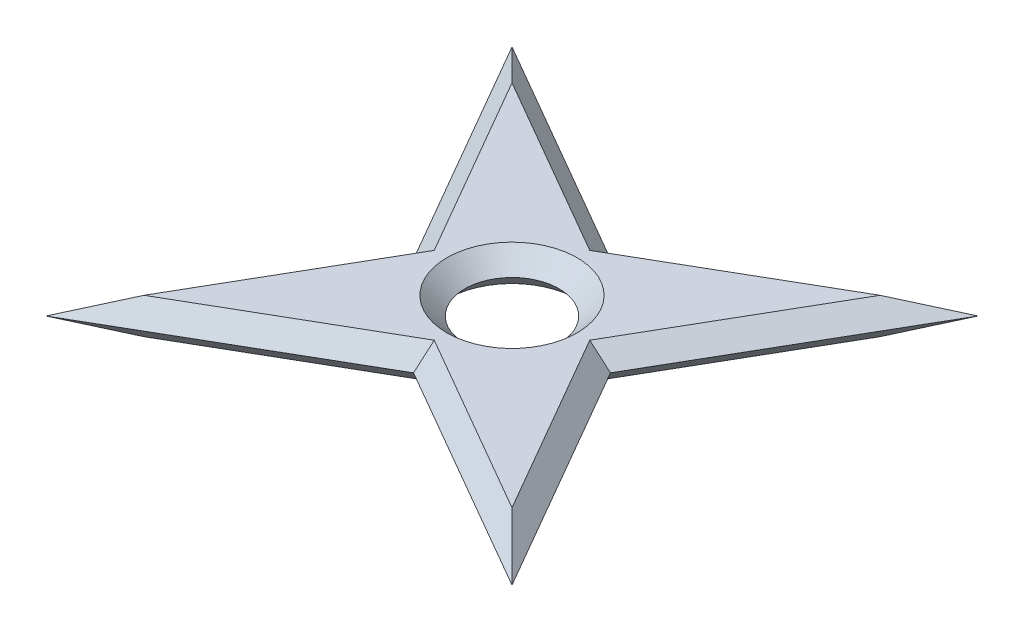
SolidWorks part; units mm, degrees
ref_plane "Front Plane" through (0, 0, 0) normal (0, 0, 1) x (1, 0, 0)
ref_plane "Top Plane" through (0, 0, 0) normal (0, 1, 0) x (1, 0, 0)
ref_plane "Right Plane" through (0, 0, 0) normal (1, 0, 0) x (0, 0, -1)
sketch "Sketch1" plane through (0, 0, 0) normal (0, 1, 0) x (1, 0, 0)
  line L0 (0, 0) -> (0, 234.4789) construction
  line L1 (0, 0) -> (250.2537, 0) construction
  line L2 (0, 0) -> (37.5, 64.9519)
  line L3 (0, 0) -> (64.9519, 37.5)
  line L5 (64.9519, 64.9519) -> (64.9519, 0) construction
  line L6 (129.9038, 0) -> (64.9519, 37.5)
  line L7 (129.9038, 0) -> (92.4038, 64.9519)
  line L8 (37.5, 64.9519) -> (92.4038, 64.9519) construction
  line L9 (129.9038, 129.9038) -> (92.4038, 64.9519)
  line L10 (129.9038, 129.9038) -> (64.9519, 92.4038)
  line L11 (0, 129.9038) -> (64.9519, 92.4038)
  line L12 (0, 129.9038) -> (37.5, 64.9519)
  circle A0 centre (64.9519, 64.9519) radius 13.155
  dimension "D5" = 26.31
  dimension "D1" = 75
  dimension "D2" = 30
  dimension "D3" = 30
  dimension "D4" = 75
extrude "Boss-Extrude1" add sketch "Sketch1" along normal blind 10
chamfer "Chamfer1" distance 5 angle 45 9 edges at (64.9519, 10, -51.7969) (18.75, 10, -32.476) (18.75, 10, -97.4279) (32.476, 10, -111.1538) (97.4279, 10, -111.1538) (111.1538, 10, -97.4279) (111.1538, 10, -32.476) (97.4279, 10, -18.75) (32.476, 10, -18.75)
chamfer "Chamfer2" distance 5 angle 45 9 edges at (64.9519, 0, -51.7969) (97.4279, 0, -18.75) (111.1538, 0, -32.476) (111.1538, 0, -97.4279) (97.4279, 0, -111.1538) (32.476, 0, -111.1538) (18.75, 0, -97.4279) (18.75, 0, -32.476) (32.476, 0, -18.75)
